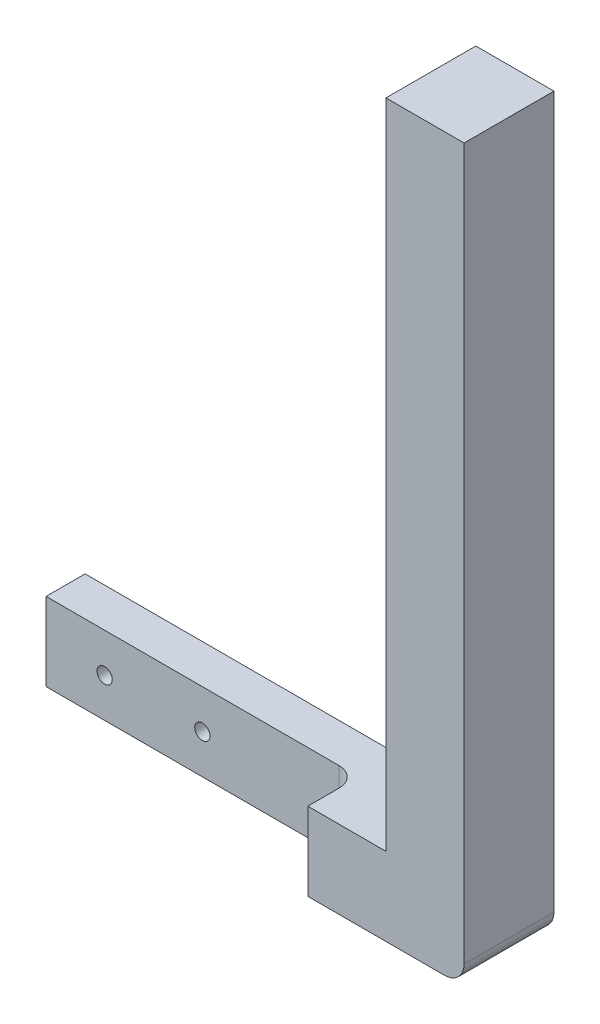
SolidWorks part; units mm, degrees
ref_plane "前基準面" through (0, 0, 0) normal (0, 0, 1) x (1, 0, 0)
ref_plane "上基準面" through (0, 0, 0) normal (0, 1, 0) x (1, 0, 0)
ref_plane "右基準面" through (0, 0, 0) normal (1, 0, 0) x (0, 0, -1)
ref_axis "基準軸1" through (0, -55, 0) along (0, 1, 0)
ref_axis "基準軸2" through (-88.99, 0, 0) along (1, 0, 0)
ref_axis "基準軸3" through (0, 0, 55) along (0, 0, -1)
sketch "草圖1" plane through (0, 0, 0) normal (0, 0, 1) x (1, 0, 0)
  line L1 (0, 0) -> (100, 0)
  line L2 (0, 0) -> (0, 20)
  line L3 (0, 20) -> (100, 20)
  line L4 (100, 0) -> (100, 20)
  circle A0 centre (15, 10) radius 1.95
  circle A1 centre (40, 10) radius 1.95
  point P9 (0, 10)
  point P10 (100, 10)
  dimension "D3" = 3.9
  dimension "D4" = 3.9
  dimension "D1" = 100
  dimension "D2" = 20
  dimension "D5" = 0
  dimension "D6" = 0
  dimension "D7" = 15
  dimension "D8" = 60
extrude "填料-伸長1" add sketch "草圖1" along normal blind 10
sketch "草圖2" plane through (0, 0, 10) normal (0, 0, 1) x (1, 0, 0)
  line L0 (100, 20) -> (0, 20) construction
  line L1 (80, 0) -> (100, 0)
  line L2 (80, 0) -> (80, 20)
  line L3 (80, 20) -> (100, 20)
  line L4 (100, 0) -> (100, 20)
  line L5 (55, 0) -> (-55, 0) construction
  line L6 (100, 0) -> (100, 20) construction
  dimension "D1" = 20
extrude "填料-伸長2" add sketch "草圖2" along normal blind 13
sketch "草圖4" plane through (0, 0, 0) normal (0, -1, 0) x (1, 0, 0)
  line L1 (100, 23) -> (120, 23)
  line L2 (100, 23) -> (100, 0)
  line L3 (100, 0) -> (120, 0)
  line L4 (120, 23) -> (120, 0)
  line L5 (-88.99, 0) -> (88.99, 0) construction
  dimension "D1" = 20
extrude "填料-伸長3" add sketch "草圖4" against normal blind 187
fillet "圓角2" radius 5 1 edges at (80, 10, 10)
fillet "圓角3" radius 5 1 edges at (120, 0, 11.5)
sketch "草圖5" plane through (0, 0, 0) normal (0, 0, 1) x (1, 0, 0)
  line L0 (120, 187) -> (100, 187) construction
  circle A0 centre (110, 177) radius 1.925
  circle A1 centre (110, 162) radius 1.925
  point P6 (110, 187)
  dimension "D1" = 3.85
  dimension "D2" = 3.85
  dimension "D5" = 10
  dimension "D6" = 15
  dimension "D3" = 0
  dimension "D4" = 0
extrude "除料-伸長1" cut sketch "草圖5" along normal blind 5
